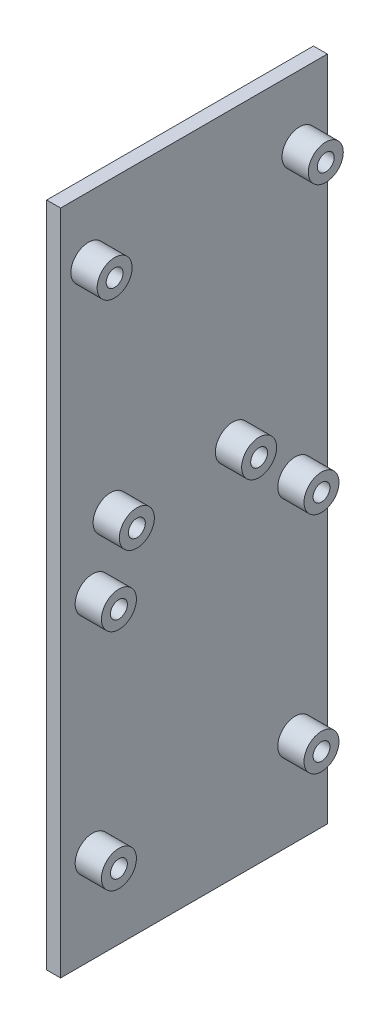
SolidWorks part; units mm, degrees
ref_plane "Front Plane" through (0, 0, 0) normal (0, 0, 1) x (1, 0, 0)
ref_plane "Top Plane" through (0, 0, 0) normal (0, 1, 0) x (1, 0, 0)
ref_plane "Right Plane" through (0, 0, 0) normal (1, 0, 0) x (0, 0, -1)
sketch "Sketch1" plane through (0, 0, 0) normal (1, 0, 0) x (0, 0, -1)
  line L1 (0, 0) -> (60.96, 0)
  line L2 (0, 0) -> (0, 152.4)
  line L3 (0, 152.4) -> (60.96, 152.4)
  line L4 (60.96, 0) -> (60.96, 152.4)
  dimension "D1" = 60.96
  dimension "D2" = 152.4
extrude "Boss-Extrude1" add sketch "Sketch1" along normal blind 3.175 contours L2 L3 L4 L1
ref_plane "Plane1" through (0, 0, -30.48) normal (0, 0, 1) x (1, 0, 0)
sketch "Sketch2" plane through (3.175, 0, 0) normal (1, 0, 0) x (0, 0, -1)
  circle A0 centre (6.35, 138.43) radius 4
  circle A1 centre (54.61, 137.16) radius 4
  circle A2 centre (11.43, 86.36) radius 4
  circle A3 centre (39.37, 86.36) radius 4
  circle A4 centre (7.33, 72.32) radius 4
  circle A5 centre (53.63, 72.32) radius 4
  circle A6 centre (7.33, 21.02) radius 4
  circle A7 centre (53.63, 21.02) radius 4
  point P0 (6.35, 138.43)
  point P1 (54.61, 137.16)
  point P3 (39.37, 86.36)
  point P5 (11.43, 86.36)
  dimension "D1" = 8
extrude "Boss-Extrude2" add sketch "Sketch2" along normal blind 6
hole_wizard "#24 (0.152) Diameter Hole1" positions "Sketch3" profile "Sketch4" hole size "#24" standard "ANSI Inch" end condition up to next
sketch "Sketch3" plane through (9.175, 0, 0) normal (1, 0, 0) x (0, 0, -1)
  point P0 (153.5671, 87.7333)
  point P2 (6.35, 138.43)
  point P5 (54.61, 137.16)
  point P8 (39.37, 86.36)
  point P11 (11.43, 86.36)
  point P14 (7.33, 72.32)
  point P17 (53.63, 72.32)
  point P20 (7.33, 21.02)
  point P23 (53.63, 21.02)
sketch "Sketch4" plane through (9.175, 87.7333, -153.5671) normal (0, 1, 0) x (0, 0, -1)
  line L0 (0, 0) -> (0, 9.175)
  line L1 (0, 9.175) -> (1.9304, 9.175)
  line L2 (1.9304, 9.175) -> (1.9304, 0)
  line L5 (1.9304, 0) -> (0, 0)
  line L11 (0, -6.35) -> (0, 107.95) construction
  dimension "Thru Hole Dia." = 3.8608
  dimension "Thru Hole Depth" = 9.175
